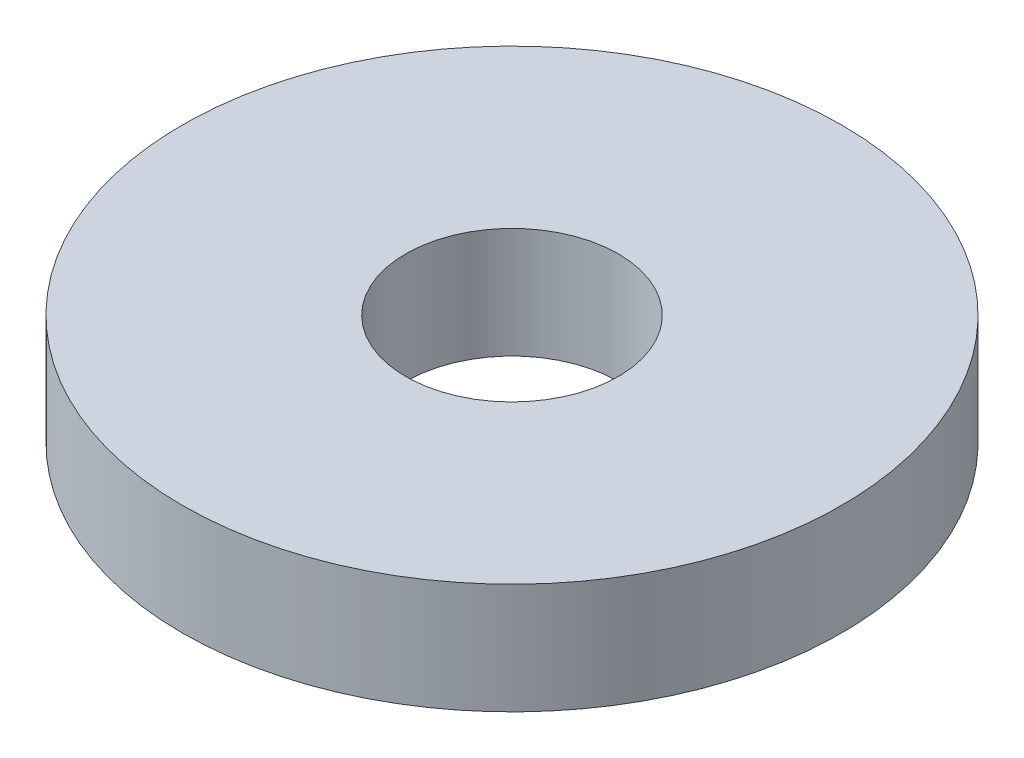
SolidWorks part; units mm, degrees
ref_plane "Front Plane" through (0, 0, 0) normal (0, 0, 1) x (1, 0, 0)
ref_plane "Top Plane" through (0, 0, 0) normal (0, 1, 0) x (1, 0, 0)
ref_plane "Right Plane" through (0, 0, 0) normal (1, 0, 0) x (0, 0, -1)
sketch "Sketch1" plane through (0, 0, 0) normal (0, 1, 0) x (1, 0, 0)
  circle A0 centre (0, 0) radius 77.5
  dimension "FLANGE_OD" = 155
extrude "Boss-Extrude1" add sketch "Sketch1" along normal blind 26
sketch "Sketch2" plane through (0, 0, 0) normal (0, 1, 0) x (1, 0, 0)
  circle A0 centre (0, 0) radius 25
  dimension "BORE_D" = 50
extrude "Cut-Extrude1" cut sketch "Sketch2" along normal through all
sketch "Sketch3" plane through (0, 26, 0) normal (0, 1, 0) x (1, 0, 0)
  circle A0 centre (0, 0) radius 18.4455 construction
  circle A1 centre (-18.4455, 0) radius 2.4041
  dimension "BOLT_D" = 4.8082
  dimension "BOLT_PCD" = 36.891
extrude "Cut-Extrude2" cut sketch "Sketch3" against normal blind 18.3201 rebuild error yes
pattern_circular "CirPattern1" count 3 over 360 rebuild error yes
